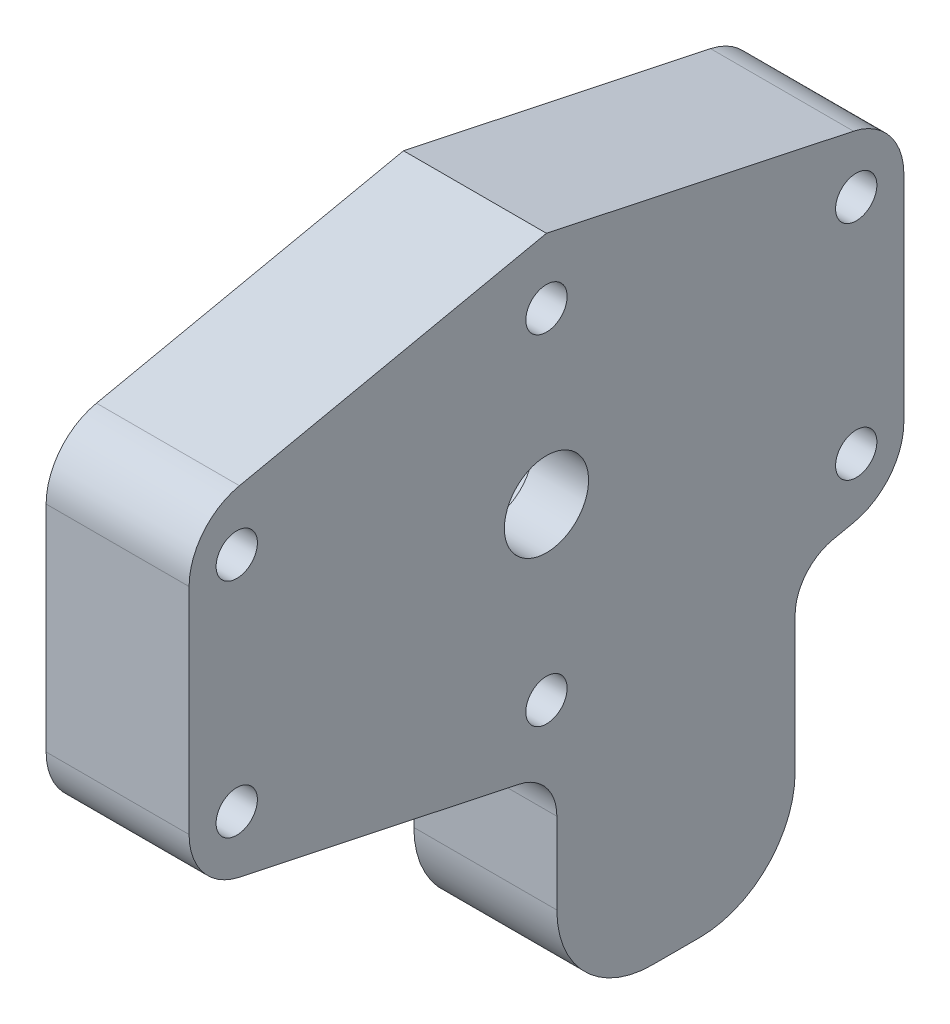
SolidWorks part; units mm, degrees
ref_plane "Front" through (0, 0, 0) normal (0, 0, 1) x (1, 0, 0)
ref_plane "Top" through (0, 0, 0) normal (0, 1, 0) x (1, 0, 0)
ref_plane "Right" through (0, 0, 0) normal (1, 0, 0) x (0, 0, -1)
sketch "Sketch1" plane through (0, 0, 0) normal (1, 0, 0) x (0, 0, -1)
  line L0 (0, -20) -> (22.5, -24.7697)
  line L1 (0, 0) -> (45, 0)
  line L2 (0, 0) -> (0, -20)
  line L3 (0, -20) -> (45, -20)
  line L4 (45, 0) -> (45, -20)
  line L5 (22.5, -24.7697) -> (45, -20)
  line L6 (22.5, 4.7697) -> (0, 0)
  line L7 (22.5, 4.7697) -> (45, 0)
  circle A0 centre (22.5, -20.6808) radius 1.3
  circle A1 centre (22.5, 0.6808) radius 1.3
  circle A2 centre (42, -17) radius 1.3
  circle A3 centre (3, -17) radius 1.3
  circle A4 centre (3, -3) radius 1.3
  circle A5 centre (42, -3) radius 1.3
  dimension "D7" = 2.6
  dimension "D8" = 2.6
  dimension "D13" = 2.6
  dimension "D1" = 45
  dimension "D2" = 20
  dimension "D3" = 23
  dimension "D4" = 23
  dimension "D5" = 23
  dimension "D6" = 23
  dimension "D9" = 4
  dimension "D10" = 4
  dimension "D11" = 4
  dimension "D12" = 4
  dimension "D14" = 3
  dimension "D15" = 3
  dimension "D16" = 2
  dimension "D17" = 2
extrude "Boss-Extrude1" add sketch "Sketch1" along normal blind 9 contours L7 L6 L1 A1 | L4 L1 L2 L3 | L0 L5 L3 A0 region at (0, -20.4525, -10.6963) region at (0, -10, -22.5) region at (0, 1.9422, -11.3438)
sketch "Sketch7" plane through (0, 0, 0) normal (-1, 0, 0) x (0, 0, 1)
  line L0 (-41.7, -10) -> (-31.3, -10)
  line L1 (-45, 0) -> (-45, -20) construction
  line L2 (-13.7, -10) -> (-3.3, -10)
  arc A0 (-31.3, -10) -> (-41.7, -10) centre (-36.5, -10) ccw
  arc A1 (-3.3, -10) -> (-13.7, -10) centre (-8.5, -10) ccw
  dimension "D1" = 10.4
  dimension "D2" = 8.5
  dimension "D3" = 10
  dimension "D4" = 2
revolve "Cut-Revolve3" cut sketch "Sketch7" angle 180 about L0 reverse direction yes
sketch "Sketch8" plane through (0, 0, 0) normal (-1, 0, 0) x (0, 0, 1)
  circle A0 centre (-22.5, -10) radius 7.6
  dimension "D1" = 15.2
  dimension "D2" = 22.5
  dimension "D3" = 10
extrude "Cut-Extrude4" cut sketch "Sketch8" against normal blind 5.5
sketch "Sketch9" plane through (5.5, 0, 0) normal (-1, 0, 0) x (0, 0, 1)
  circle A0 centre (-22.5, -10) radius 2.65
  dimension "D1" = 5.3
extrude "Cut-Extrude5" cut sketch "Sketch9" against normal through all
sketch "Sketch16" plane through (9, 0, 0) normal (1, 0, 0) x (0, 0, -1)
  line L0 (38.1522, -21.4516) -> (38.1522, -38.4516)
  line L1 (22.5, -24.7697) -> (45, -20) construction
  line L2 (38.1522, -38.4516) -> (23.1522, -38.4516)
  line L3 (23.1522, -38.4516) -> (23.1522, -24.6314)
  line L4 (23.1522, -24.6314) -> (38.1522, -21.4516)
  dimension "D1" = 17
  dimension "D2" = 15
  dimension "D3" = 7
extrude "Boss-Extrude7" add sketch "Sketch16" against normal blind 9
sketch "Sketch17" plane through (0, 0, 0) normal (-1, 0, 0) x (0, 0, 1)
  line L0 (-38.1522, -38.4516) -> (-38.1522, -21.4516) construction
  line L1 (-23.1522, -38.4516) -> (-38.1522, -38.4516) construction
  line L2 (-25.4522, -30.4516) -> (-35.8522, -30.4516)
  arc A0 (-25.4522, -30.4516) -> (-35.8522, -30.4516) centre (-30.6522, -30.4516) ccw
  dimension "D1" = 10.4
  dimension "D2" = 7.5
  dimension "D3" = 8
revolve "Cut-Revolve4" cut sketch "Sketch17" angle 180 about L2
fillet "Fillet1" radius 6 2 edges at (4.5, -38.4516, -23.1522) (4.5, -38.4516, -38.1522)
fillet "Fillet2" radius 4 4 edges at (4.5, -20, -45) (4.5, 0, -45) (4.5, 0, 0) (4.5, -20, 0)
fillet "Fillet3" radius 3 2 edges at (4.5, -21.4516, -38.1522) (4.5, -24.6314, -23.1522)
fillet "Fillet4" radius 3 1 edges at (4.5, -24.7697, -22.5)
